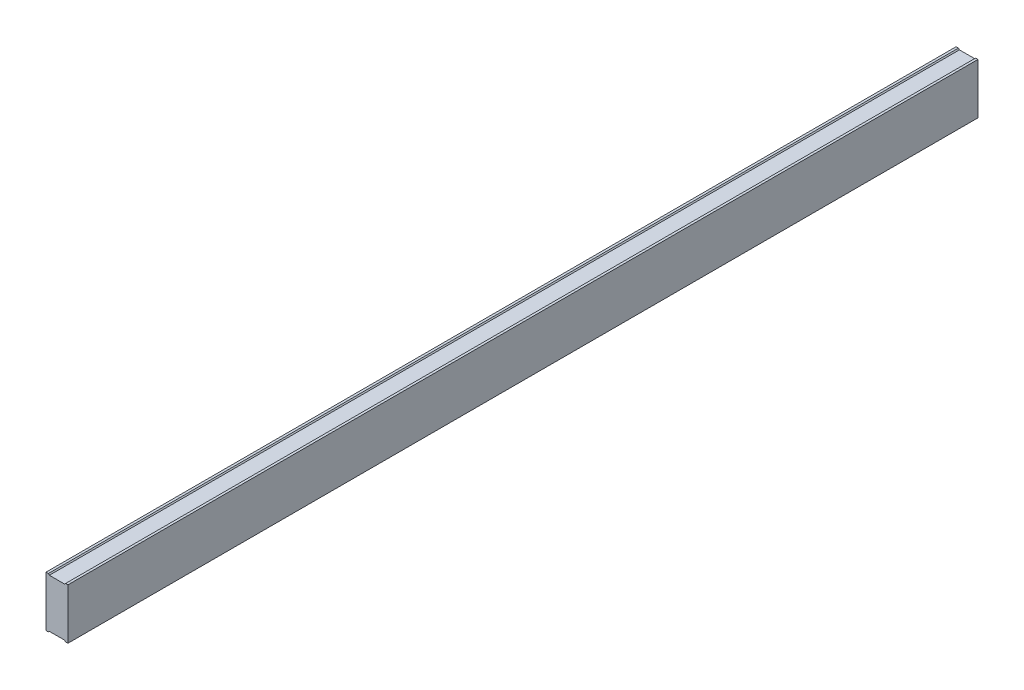
SolidWorks part; units mm, degrees
material "6061-T6 (SS)"
ref_plane "前视基准面" through (0, 0, 0) normal (0, 0, 1) x (1, 0, 0)
ref_plane "上视基准面" through (0, 0, 0) normal (0, 1, 0) x (1, 0, 0)
ref_plane "右视基准面" through (0, 0, 0) normal (1, 0, 0) x (0, 0, -1)
sketch "Model" plane through (0, 0, 0) normal (0, 0, 1) x (1, 0, 0)
  line L0 (11746.24, -58203.4132) -> (11636.4348, -58203.4132) construction
  line L1 (11739.24, -58278.4132) -> (11736.24, -58275.4132)
  line L11 (11746.24, -58128.4132) -> (11746.24, -58278.4132)
  line L12 (11739.24, -58128.4132) -> (11746.24, -58128.4132)
  line L13 (11739.24, -58128.4132) -> (11736.24, -58131.4132)
  line L14 (11691.24, -58131.4132) -> (11736.24, -58131.4132)
  line L15 (11688.24, -58128.4132) -> (11691.24, -58131.4132)
  line L16 (11688.24, -58128.4132) -> (11681.24, -58128.4132)
  line L17 (11681.24, -58128.4132) -> (11681.24, -58136.4132)
  line L18 (11681.24, -58136.4132) -> (11739.24, -58136.4132)
  line L19 (11742.24, -58139.4132) -> (11742.24, -58267.4132)
  line L20 (11739.24, -58278.4132) -> (11746.24, -58278.4132)
  line L23 (11681.24, -58270.4132) -> (11739.24, -58270.4132)
  line L24 (11681.24, -58278.4132) -> (11681.24, -58270.4132)
  line L25 (11688.24, -58278.4132) -> (11681.24, -58278.4132)
  line L26 (11688.24, -58278.4132) -> (11691.24, -58275.4132)
  line L27 (11691.24, -58275.4132) -> (11736.24, -58275.4132)
  arc A2 (11742.24, -58139.4132) -> (11739.24, -58136.4132) centre (11739.24, -58139.4132) ccw
  arc A3 (11742.24, -58267.4132) -> (11739.24, -58270.4132) centre (11739.24, -58267.4132) cw
  point P12 (11742.24, -58203.4132)
  point P16 (11742.74, -58278.4132)
  dimension "D8" = 3
  dimension "D1" = 150
  dimension "D2" = 4
  dimension "D3" = 65
  dimension "D4" = 8
  dimension "D5" = 7
  dimension "D6" = 10
  dimension "D7" = 5
extrude "凸台-拉伸1" add sketch "Model" along normal blind 2697 contours L11 L20 L1 L27 L26 L25 L24 L23 A3 L19 A2 L18 L17 L16 L15 L14 L13 L12
sketch "草图2" plane through (0, 0, 2697) normal (0, 0, 1) x (1, 0, 0)
  line L0 (11681.24, -58270.4132) -> (11739.24, -58270.4132) construction
  line L1 (11681.24, -58136.4132) -> (11742.24, -58136.4132)
  line L2 (11681.24, -58136.4132) -> (11681.24, -58270.4132)
  line L3 (11681.24, -58270.4132) -> (11742.24, -58270.4132)
  line L4 (11742.24, -58136.4132) -> (11742.24, -58270.4132)
  line L5 (11742.24, -58139.4132) -> (11742.24, -58267.4132) construction
extrude "凸台-拉伸2" add sketch "草图2" against normal blind 6
sketch "草图3" plane through (0, 0, 0) normal (0, 0, -1) x (-1, 0, 0)
  line L0 (-11681.24, -58270.4132) -> (-11739.24, -58270.4132) construction
  line L1 (-11681.24, -58136.4132) -> (-11742.24, -58136.4132)
  line L2 (-11681.24, -58136.4132) -> (-11681.24, -58270.4132)
  line L3 (-11681.24, -58270.4132) -> (-11742.24, -58270.4132)
  line L4 (-11742.24, -58136.4132) -> (-11742.24, -58270.4132)
  line L5 (-11742.24, -58139.4132) -> (-11742.24, -58267.4132) construction
extrude "凸台-拉伸3" add sketch "草图3" against normal blind 6
sketch "Sketch1" plane through (11742.24, 0, 0) normal (-1, 0, 0) x (0, 0, 1)
  line L0 (2697, -58128.4132) -> (2697, -58278.4132) construction
  line L1 (2697, -58128.4132) -> (0, -58128.4132) construction
  circle A0 centre (2497, -58203.4132) radius 8
  dimension "D1" = 16
  dimension "D2" = 75
  dimension "D3" = 200
extrude "TX1" [suppressed] cut sketch "Sketch1" against normal up to next
sketch "Sketch2" [suppressed] plane through (11742.24, 0, 0) normal (-1, 0, 0) x (0, 0, 1)
  line L0 (2697, -58128.4132) -> (0, -58128.4132) construction
  circle A0 centre (2405.9292, -58203.4132) radius 8
  circle A4 centre (2497, -58203.4132) radius 8 construction
  dimension "D1" = 16
  dimension "D2" = 75
  dimension "D3" = 91.0708
extrude "TX2" [suppressed] cut sketch "Sketch2" against normal up to next
sketch "Sketch3" [suppressed] plane through (11742.24, 0, 0) normal (-1, 0, 0) x (0, 0, 1)
  line L1 (2697, -58128.4132) -> (0, -58128.4132) construction
  circle A0 centre (2331.9405, -58203.4132) radius 8
  circle A1 centre (2405.9292, -58203.4132) radius 8 construction
  dimension "D1" = 16
  dimension "D2" = 75
  dimension "D3" = 73.9888
extrude "TX3" [suppressed] cut sketch "Sketch3" against normal up to next
sketch "Sketch4" [suppressed] plane through (11742.24, 0, 0) normal (-1, 0, 0) x (0, 0, 1)
  line L1 (2697, -58128.4132) -> (0, -58128.4132) construction
  circle A0 centre (2272.4022, -58203.4132) radius 8
  circle A1 centre (2331.9405, -58203.4132) radius 8 construction
  dimension "D1" = 16
  dimension "D2" = 75
  dimension "D3" = 59.5383
extrude "TX4" [suppressed] cut sketch "Sketch4" against normal up to next
sketch "Sketch5" [suppressed] plane through (11742.24, 0, 0) normal (-1, 0, 0) x (0, 0, 1)
  line L1 (2697, -58128.4132) -> (0, -58128.4132) construction
  circle A0 centre (2218.3734, -58203.4132) radius 8
  circle A1 centre (2272.4022, -58203.4132) radius 8 construction
  dimension "D1" = 16
  dimension "D2" = 75
  dimension "D3" = 54.0288
extrude "TX5" [suppressed] cut sketch "Sketch5" against normal up to next
sketch "Sketch6" [suppressed] plane through (11742.24, 0, 0) normal (-1, 0, 0) x (0, 0, 1)
  line L1 (2697, -58128.4132) -> (0, -58128.4132) construction
  circle A0 centre (2174.8914, -58203.4132) radius 8
  circle A1 centre (2218.3734, -58203.4132) radius 8 construction
  dimension "D1" = 16
  dimension "D2" = 75
  dimension "D3" = 43.482
extrude "TX6" [suppressed] cut sketch "Sketch6" against normal up to next
sketch "Sketch7" [suppressed] plane through (11742.24, 0, 0) normal (-1, 0, 0) x (0, 0, 1)
  line L1 (2697, -58128.4132) -> (0, -58128.4132) construction
  circle A0 centre (2131.6645, -58203.4132) radius 8
  circle A1 centre (2174.8914, -58203.4132) radius 8 construction
  dimension "D1" = 16
  dimension "D2" = 75
  dimension "D3" = 43.2269
extrude "TX7" [suppressed] cut sketch "Sketch7" against normal up to next
sketch "Sketch8" [suppressed] plane through (11742.24, 0, 0) normal (-1, 0, 0) x (0, 0, 1)
  line L1 (2697, -58128.4132) -> (0, -58128.4132) construction
  circle A0 centre (2085.6036, -58203.4132) radius 8
  circle A1 centre (2131.6645, -58203.4132) radius 8 construction
  dimension "D1" = 16
  dimension "D2" = 75
  dimension "D3" = 46.061
extrude "TX8" [suppressed] cut sketch "Sketch8" against normal up to next
sketch "Sketch9" plane through (0, -58131.4132, 0) normal (0, 1, 0) x (1, 0, 0)
  line L0 (11746.24, -2697) -> (11746.24, 0) construction
  line L1 (11691.24, -2697) -> (11736.24, -2697) construction
  circle A0 centre (11713.74, -2647) radius 8
  dimension "D1" = 16
  dimension "D2" = 32.5
  dimension "D3" = 50
extrude "FLX1" [suppressed] cut sketch "Sketch9" against normal up to next
sketch "Sketch10" [suppressed] plane through (0, -58131.4132, 0) normal (0, 1, 0) x (1, 0, 0)
  line L0 (11746.24, -2697) -> (11746.24, 0) construction
  circle A0 centre (11713.74, -2597) radius 8
  circle A1 centre (11713.74, -2647) radius 8 construction
  dimension "D1" = 16
  dimension "D2" = 32.5
  dimension "D3" = 50
extrude "FLX2" [suppressed] cut sketch "Sketch10" against normal up to next
sketch "Sketch11" plane through (0, -58131.4132, 0) normal (0, 1, 0) x (1, 0, 0)
  line L0 (11746.24, -2697) -> (11746.24, 0) construction
  line L1 (11691.24, 0) -> (11736.24, 0) construction
  circle A0 centre (11713.74, -50) radius 8
  dimension "D1" = 16
  dimension "D2" = 32.5
  dimension "D3" = 50
extrude "FRX1" [suppressed] cut sketch "Sketch11" against normal up to next
sketch "Sketch12" [suppressed] plane through (0, -58131.4132, 0) normal (0, 1, 0) x (1, 0, 0)
  line L0 (11746.24, -2697) -> (11746.24, 0) construction
  circle A0 centre (11713.74, -100) radius 8
  circle A1 centre (11713.74, -50) radius 8 construction
  dimension "D1" = 16
  dimension "D2" = 32.5
  dimension "D3" = 50
extrude "FRX2" [suppressed] cut sketch "Sketch12" against normal up to next
sketch "Sketch13" plane through (0, -58275.4132, 0) normal (0, -1, 0) x (1, 0, 0)
  line L0 (11746.24, 2697) -> (11746.24, 0) construction
  line L1 (11691.24, 2697) -> (11736.24, 2697) construction
  circle A0 centre (11713.74, 2647) radius 8
  dimension "D1" = 16
  dimension "D2" = 32.5
  dimension "D3" = 50
extrude "BLX1" [suppressed] cut sketch "Sketch13" against normal up to next
sketch "Sketch14" [suppressed] plane through (0, -58275.4132, 0) normal (0, -1, 0) x (1, 0, 0)
  line L0 (11746.24, 2697) -> (11746.24, 0) construction
  circle A0 centre (11713.74, 2597) radius 8
  circle A1 centre (11713.74, 2647) radius 8 construction
  dimension "D1" = 16
  dimension "D2" = 32.5
  dimension "D3" = 50
extrude "BLX2" [suppressed] cut sketch "Sketch14" against normal up to next
sketch "Sketch15" plane through (0, -58275.4132, 0) normal (0, -1, 0) x (1, 0, 0)
  line L0 (11746.24, 2697) -> (11746.24, 0) construction
  line L1 (11691.24, 0) -> (11736.24, 0) construction
  circle A0 centre (11713.74, 50) radius 8
  dimension "D1" = 16
  dimension "D2" = 32.5
  dimension "D3" = 50
extrude "BRX1" [suppressed] cut sketch "Sketch15" against normal up to next
sketch "Sketch16" [suppressed] plane through (0, -58275.4132, 0) normal (0, -1, 0) x (1, 0, 0)
  line L0 (11746.24, 2697) -> (11746.24, 0) construction
  circle A0 centre (11713.74, 100) radius 8
  circle A1 centre (11713.74, 50) radius 8 construction
  dimension "D1" = 16
  dimension "D2" = 32.5
  dimension "D3" = 50
extrude "BRX2" [suppressed] cut sketch "Sketch16" against normal up to next
sketch "Sketch17" plane through (0, 0, 2697) normal (0, 0, 1) x (1, 0, 0)
  line L0 (11746.24, -58128.4132) -> (11746.24, -58278.4132) construction
  line L1 (11739.24, -58278.4132) -> (11746.24, -58278.4132) construction
  circle A0 centre (11713.74, -58228.4132) radius 8
  dimension "D1" = 16
  dimension "D2" = 32.5
  dimension "D3" = 50
extrude "LBY1" [suppressed] cut sketch "Sketch17" against normal up to next
sketch "Sketch18" [suppressed] plane through (0, 0, 2697) normal (0, 0, 1) x (1, 0, 0)
  line L0 (11746.24, -58128.4132) -> (11746.24, -58278.4132) construction
  circle A0 centre (11713.74, -58178.4132) radius 8
  circle A1 centre (11713.74, -58228.4132) radius 8 construction
  dimension "D1" = 16
  dimension "D2" = 32.5
  dimension "D3" = 50
extrude "LBY2" [suppressed] cut sketch "Sketch18" against normal up to next
sketch "Sketch19" plane through (0, 0, 2697) normal (0, 0, 1) x (1, 0, 0)
  line L0 (11746.24, -58128.4132) -> (11746.24, -58278.4132) construction
  line L1 (11739.24, -58128.4132) -> (11746.24, -58128.4132) construction
  circle A0 centre (11713.74, -58178.4132) radius 8
  dimension "D1" = 16
  dimension "D2" = 32.5
  dimension "D3" = 50
extrude "LFY1" [suppressed] cut sketch "Sketch19" against normal up to next
sketch "Sketch20" [suppressed] plane through (0, 0, 2697) normal (0, 0, 1) x (1, 0, 0)
  line L0 (11746.24, -58128.4132) -> (11746.24, -58278.4132) construction
  circle A0 centre (11713.74, -58228.4132) radius 8
  circle A1 centre (11713.74, -58178.4132) radius 8 construction
  dimension "D1" = 16
  dimension "D2" = 32.5
  dimension "D3" = 50
extrude "LFY2" [suppressed] cut sketch "Sketch20" against normal up to next
sketch "Sketch21" plane through (0, 0, 0) normal (0, 0, -1) x (-1, 0, 0)
  line L0 (-11746.24, -58128.4132) -> (-11746.24, -58278.4132) construction
  line L1 (-11739.24, -58278.4132) -> (-11746.24, -58278.4132) construction
  circle A0 centre (-11713.74, -58228.4132) radius 8
  dimension "D1" = 16
  dimension "D2" = 32.5
  dimension "D3" = 50
extrude "RBY1" [suppressed] cut sketch "Sketch21" against normal up to next
sketch "Sketch22" [suppressed] plane through (0, 0, 0) normal (0, 0, -1) x (-1, 0, 0)
  line L0 (-11746.24, -58128.4132) -> (-11746.24, -58278.4132) construction
  circle A0 centre (-11713.74, -58178.4132) radius 8
  circle A1 centre (-11713.74, -58228.4132) radius 8 construction
  dimension "D1" = 16
  dimension "D2" = 32.5
  dimension "D3" = 50
extrude "RBY2" [suppressed] cut sketch "Sketch22" against normal up to next
sketch "Sketch23" plane through (0, 0, 0) normal (0, 0, -1) x (-1, 0, 0)
  line L1 (-11746.24, -58128.4132) -> (-11746.24, -58278.4132) construction
  line L2 (-11739.24, -58128.4132) -> (-11746.24, -58128.4132) construction
  circle A0 centre (-11713.74, -58178.4132) radius 8
  dimension "D1" = 16
  dimension "D2" = 32.5
  dimension "D3" = 50
extrude "RFY1" [suppressed] cut sketch "Sketch23" against normal up to next
sketch "Sketch24" [suppressed] plane through (0, 0, 0) normal (0, 0, -1) x (-1, 0, 0)
  line L0 (-11746.24, -58128.4132) -> (-11746.24, -58278.4132) construction
  circle A0 centre (-11713.74, -58228.4132) radius 8
  circle A1 centre (-11713.74, -58178.4132) radius 8 construction
  dimension "D1" = 16
  dimension "D2" = 32.5
  dimension "D3" = 50
extrude "RFY2" [suppressed] cut sketch "Sketch24" against normal up to next
